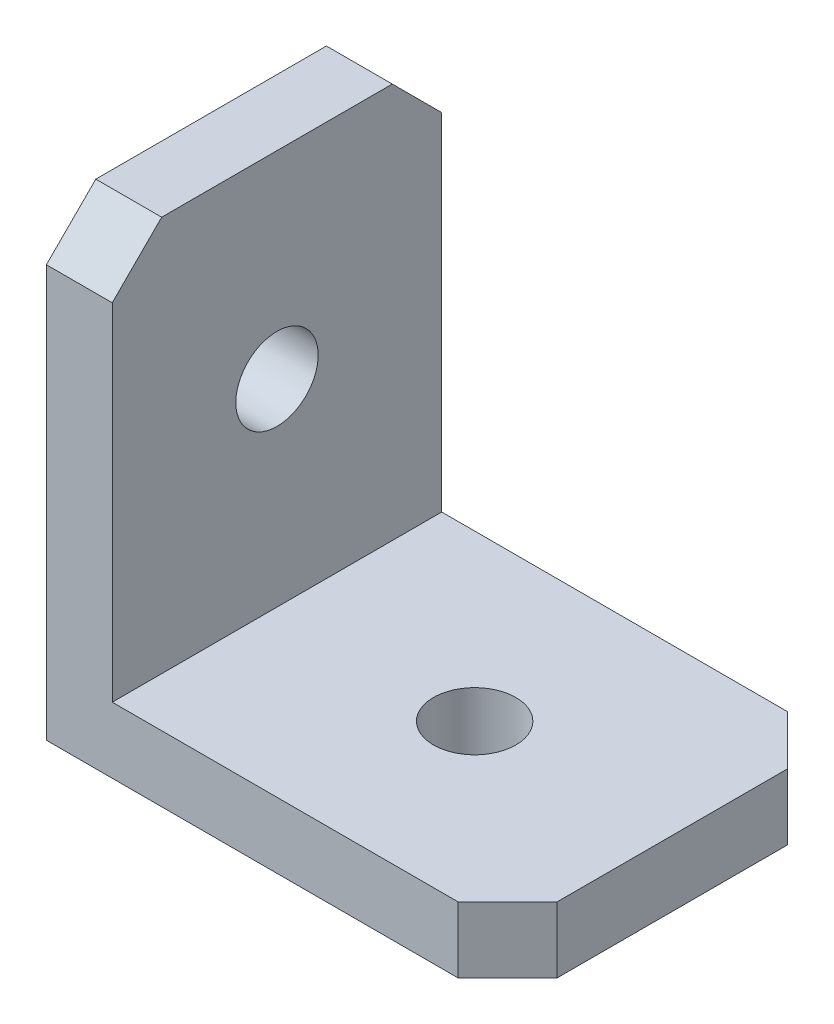
SolidWorks part; units mm, degrees
material "1060 Alloy"
ref_plane "Front Plane" through (0, 0, 0) normal (0, 0, 1) x (1, 0, 0)
ref_plane "Top Plane" through (0, 0, 0) normal (0, 1, 0) x (1, 0, 0)
ref_plane "Right Plane" through (0, 0, 0) normal (1, 0, 0) x (0, 0, -1)
sketch "Sketch1" plane through (0, 0, 0) normal (0, 0, 1) x (1, 0, 0)
  line L0 (0, 0) -> (0, 14)
  line L1 (0, 14) -> (2, 14)
  line L2 (2, 14) -> (2, 2)
  line L3 (2, 2) -> (14, 2)
  line L4 (14, 2) -> (14, 0)
  line L5 (14, 0) -> (0, 0)
  dimension "D1" = 2
  dimension "D2" = 14
extrude "Boss-Extrude1" add sketch "Sketch1" along normal mid plane 10
chamfer "Chamfer1" distance 1.5 angle 45 4 edges at (14, 1, -5) (14, 1, 5) (1, 14, -5) (1, 14, 5)
sketch "Sketch2" plane through (0, 0, 0) normal (-1, 0, 0) x (0, 0, 1)
  line L0 (5, 0) -> (-5, 0) construction
  circle A0 centre (0, 8) radius 1.25
  point P4 (0, 0)
  dimension "D1" = 2.5
  dimension "D2" = 8
extrude "Cut-Extrude1" cut sketch "Sketch2" against normal through all
cosmetic thread "Cosmetic Thread1" parameters "D2"=3
sketch "Sketch3" plane through (0, 0, 0) normal (0, -1, 0) x (1, 0, 0)
  line L0 (0, 5) -> (0, -5) construction
  circle A0 centre (8, 0) radius 1.25
  dimension "D1" = 2.5
  dimension "D2" = 8
extrude "Cut-Extrude2" cut sketch "Sketch3" against normal blind 10
cosmetic thread "Cosmetic Thread2" parameters "D2"=3
